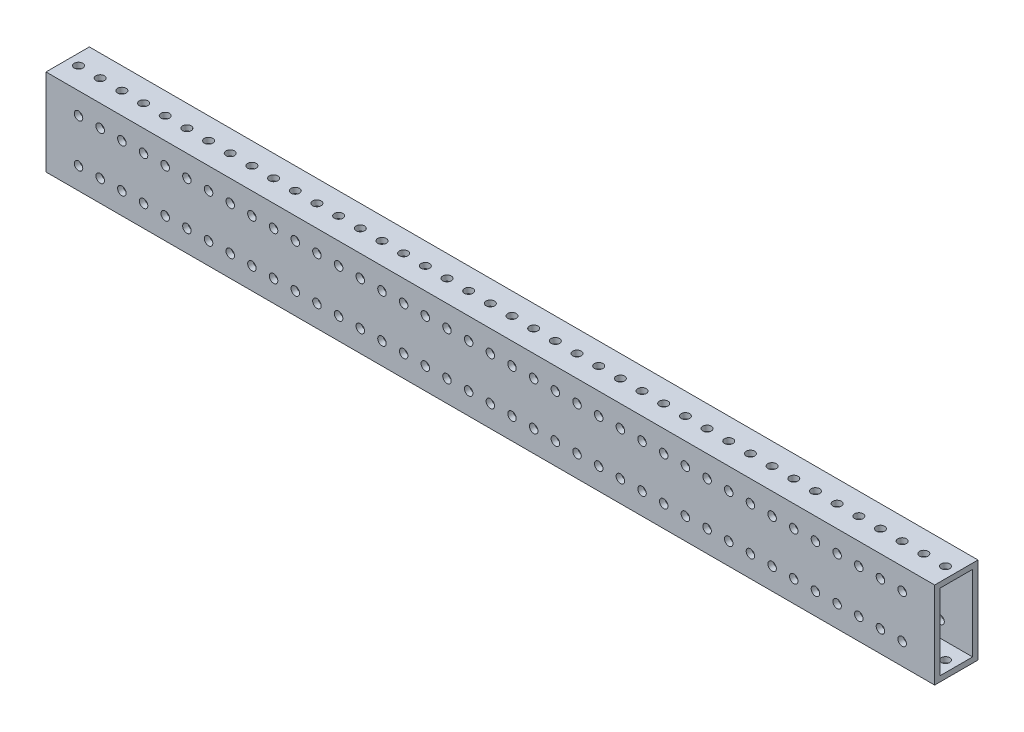
SolidWorks part; units mm, degrees
material "6061-T6 (SS)"
ref_plane "Front Plane" through (0, 0, 0) normal (0, 0, 1) x (1, 0, 0)
ref_plane "Top Plane" through (0, 0, 0) normal (0, 1, 0) x (1, 0, 0)
ref_plane "Right Plane" through (0, 0, 0) normal (1, 0, 0) x (0, 0, -1)
sketch "Sketch1" plane through (0, 0, 0) normal (0, 0, 1) x (1, 0, 0)
  line L1 (0, 0) -> (520.7, 0)
  line L2 (0, 0) -> (0, 50.8)
  line L3 (0, 50.8) -> (520.7, 50.8)
  line L4 (520.7, 0) -> (520.7, 50.8)
  dimension "D1" = 50.8
  dimension "D2" = 520.7
extrude "Boss-Extrude1" add sketch "Sketch1" along normal blind 25.4
shell "Shell1" thickness 3.175 removed face at (520.7, 25.4, 12.7) removed face at (0, 25.4, 12.7)
sketch "Sketch2" plane through (0, 0, 0) normal (0, 0, -1) x (-1, 0, 0)
  line L0 (-520.7, 50.8) -> (0, 50.8) construction
  line L1 (-520.7, 0) -> (-520.7, 50.8) construction
  circle A0 centre (-501.65, 38.1) radius 2.4892
  circle A1 centre (-488.95, 38.1) radius 2.4892
  circle A2 centre (-476.25, 38.1) radius 2.4892
  circle A3 centre (-463.55, 38.1) radius 2.4892
  circle A4 centre (-450.85, 38.1) radius 2.4892
  circle A5 centre (-438.15, 38.1) radius 2.4892
  circle A6 centre (-425.45, 38.1) radius 2.4892
  circle A7 centre (-412.75, 38.1) radius 2.4892
  circle A8 centre (-400.05, 38.1) radius 2.4892
  circle A9 centre (-387.35, 38.1) radius 2.4892
  circle A10 centre (-374.65, 38.1) radius 2.4892
  circle A11 centre (-361.95, 38.1) radius 2.4892
  circle A12 centre (-349.25, 38.1) radius 2.4892
  circle A13 centre (-336.55, 38.1) radius 2.4892
  circle A14 centre (-323.85, 38.1) radius 2.4892
  circle A15 centre (-311.15, 38.1) radius 2.4892
  circle A16 centre (-298.45, 38.1) radius 2.4892
  circle A17 centre (-285.75, 38.1) radius 2.4892
  circle A18 centre (-273.05, 38.1) radius 2.4892
  circle A19 centre (-260.35, 38.1) radius 2.4892
  circle A20 centre (-247.65, 38.1) radius 2.4892
  circle A21 centre (-234.95, 38.1) radius 2.4892
  circle A22 centre (-222.25, 38.1) radius 2.4892
  circle A23 centre (-209.55, 38.1) radius 2.4892
  circle A24 centre (-196.85, 38.1) radius 2.4892
  circle A25 centre (-184.15, 38.1) radius 2.4892
  circle A26 centre (-171.45, 38.1) radius 2.4892
  circle A27 centre (-158.75, 38.1) radius 2.4892
  circle A28 centre (-146.05, 38.1) radius 2.4892
  circle A29 centre (-133.35, 38.1) radius 2.4892
  circle A30 centre (-120.65, 38.1) radius 2.4892
  circle A31 centre (-107.95, 38.1) radius 2.4892
  circle A32 centre (-95.25, 38.1) radius 2.4892
  circle A33 centre (-82.55, 38.1) radius 2.4892
  circle A34 centre (-69.85, 38.1) radius 2.4892
  circle A35 centre (-57.15, 38.1) radius 2.4892
  circle A36 centre (-44.45, 38.1) radius 2.4892
  circle A37 centre (-31.75, 38.1) radius 2.4892
  circle A38 centre (-19.05, 38.1) radius 2.4892
  circle A40 centre (-488.95, 12.7) radius 2.4892
  circle A41 centre (-476.25, 12.7) radius 2.4892
  circle A42 centre (-463.55, 12.7) radius 2.4892
  circle A43 centre (-450.85, 12.7) radius 2.4892
  circle A44 centre (-438.15, 12.7) radius 2.4892
  circle A45 centre (-425.45, 12.7) radius 2.4892
  circle A46 centre (-412.75, 12.7) radius 2.4892
  circle A47 centre (-400.05, 12.7) radius 2.4892
  circle A48 centre (-387.35, 12.7) radius 2.4892
  circle A49 centre (-374.65, 12.7) radius 2.4892
  circle A50 centre (-361.95, 12.7) radius 2.4892
  circle A51 centre (-349.25, 12.7) radius 2.4892
  circle A52 centre (-336.55, 12.7) radius 2.4892
  circle A53 centre (-323.85, 12.7) radius 2.4892
  circle A54 centre (-311.15, 12.7) radius 2.4892
  circle A55 centre (-298.45, 12.7) radius 2.4892
  circle A56 centre (-285.75, 12.7) radius 2.4892
  circle A57 centre (-273.05, 12.7) radius 2.4892
  circle A58 centre (-260.35, 12.7) radius 2.4892
  circle A59 centre (-247.65, 12.7) radius 2.4892
  circle A60 centre (-234.95, 12.7) radius 2.4892
  circle A61 centre (-222.25, 12.7) radius 2.4892
  circle A62 centre (-209.55, 12.7) radius 2.4892
  circle A63 centre (-196.85, 12.7) radius 2.4892
  circle A64 centre (-184.15, 12.7) radius 2.4892
  circle A65 centre (-171.45, 12.7) radius 2.4892
  circle A66 centre (-158.75, 12.7) radius 2.4892
  circle A67 centre (-146.05, 12.7) radius 2.4892
  circle A68 centre (-133.35, 12.7) radius 2.4892
  circle A69 centre (-120.65, 12.7) radius 2.4892
  circle A70 centre (-107.95, 12.7) radius 2.4892
  circle A71 centre (-95.25, 12.7) radius 2.4892
  circle A72 centre (-82.55, 12.7) radius 2.4892
  circle A73 centre (-69.85, 12.7) radius 2.4892
  circle A74 centre (-57.15, 12.7) radius 2.4892
  circle A75 centre (-44.45, 12.7) radius 2.4892
  circle A76 centre (-31.75, 12.7) radius 2.4892
  circle A77 centre (-19.05, 12.7) radius 2.4892
  circle A79 centre (-501.65, 12.7) radius 2.4892
  circle A80 centre (-6.35, 38.1) radius 2.4892 [skipped]
  circle A81 centre (-6.35, 12.7) radius 2.4892 [skipped]
  dimension "D1" = 4.9784
  dimension "D3" = 19.05
  dimension "D2" = 12.7
  dimension "D6" = 25.4
  dimension "D7" = 12.7
  dimension "D4" = 40
  dimension "D5" = 2
extrude "Cut-Extrude1" cut sketch "Sketch2" against normal blind 25.4
sketch "Sketch3" plane through (0, 50.8, 0) normal (0, 1, 0) x (1, 0, 0)
  line L0 (0, -25.4) -> (0, 0) construction
  line L1 (520.7, 0) -> (0, 0) construction
  line L2 (520.7, -25.4) -> (520.7, 0) construction
  circle A0 centre (6.35, -12.7) radius 2.4892
  circle A1 centre (19.05, -12.7) radius 2.4892
  circle A2 centre (31.75, -12.7) radius 2.4892
  circle A3 centre (44.45, -12.7) radius 2.4892
  circle A4 centre (57.15, -12.7) radius 2.4892
  circle A5 centre (69.85, -12.7) radius 2.4892
  circle A6 centre (82.55, -12.7) radius 2.4892
  circle A7 centre (95.25, -12.7) radius 2.4892
  circle A8 centre (107.95, -12.7) radius 2.4892
  circle A9 centre (120.65, -12.7) radius 2.4892
  circle A10 centre (133.35, -12.7) radius 2.4892
  circle A11 centre (146.05, -12.7) radius 2.4892
  circle A12 centre (158.75, -12.7) radius 2.4892
  circle A13 centre (171.45, -12.7) radius 2.4892
  circle A14 centre (184.15, -12.7) radius 2.4892
  circle A15 centre (196.85, -12.7) radius 2.4892
  circle A16 centre (209.55, -12.7) radius 2.4892
  circle A17 centre (222.25, -12.7) radius 2.4892
  circle A18 centre (234.95, -12.7) radius 2.4892
  circle A19 centre (247.65, -12.7) radius 2.4892
  circle A20 centre (260.35, -12.7) radius 2.4892
  circle A21 centre (273.05, -12.7) radius 2.4892
  circle A22 centre (285.75, -12.7) radius 2.4892
  circle A23 centre (298.45, -12.7) radius 2.4892
  circle A24 centre (311.15, -12.7) radius 2.4892
  circle A25 centre (323.85, -12.7) radius 2.4892
  circle A26 centre (336.55, -12.7) radius 2.4892
  circle A27 centre (349.25, -12.7) radius 2.4892
  circle A28 centre (361.95, -12.7) radius 2.4892
  circle A29 centre (374.65, -12.7) radius 2.4892
  circle A30 centre (387.35, -12.7) radius 2.4892
  circle A31 centre (400.05, -12.7) radius 2.4892
  circle A32 centre (412.75, -12.7) radius 2.4892
  circle A33 centre (425.45, -12.7) radius 2.4892
  circle A34 centre (438.15, -12.7) radius 2.4892
  circle A35 centre (450.85, -12.7) radius 2.4892
  circle A36 centre (463.55, -12.7) radius 2.4892
  circle A37 centre (476.25, -12.7) radius 2.4892
  circle A38 centre (488.95, -12.7) radius 2.4892
  circle A39 centre (501.65, -12.7) radius 2.4892
  circle A40 centre (514.35, -12.7) radius 2.4892
  dimension "D1" = 4.9784
  dimension "D2" = 6.35
  dimension "D3" = 12.7
  dimension "D5" = 12.7
  dimension "D6" = 6.35
  dimension "D4" = 40
extrude "Cut-Extrude2" cut sketch "Sketch3" against normal blind 50.8
